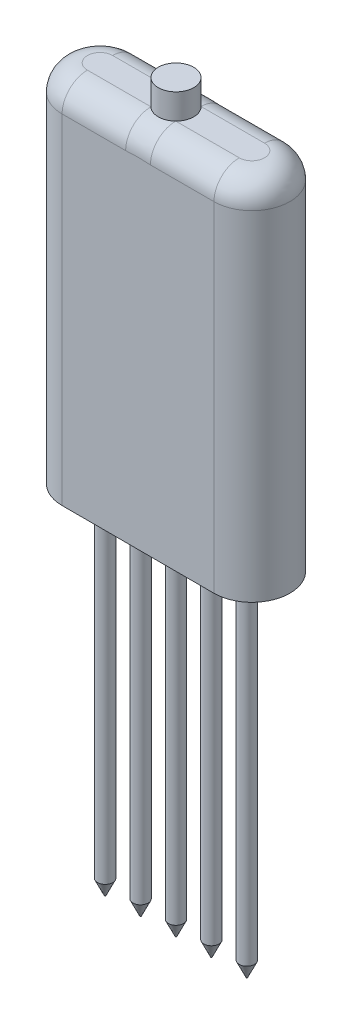
SolidWorks part; units mm, degrees
ref_plane "Front Plane" through (0, 0, 0) normal (0, 0, 1) x (1, 0, 0)
ref_plane "Top Plane" through (0, 0, 0) normal (0, 1, 0) x (1, 0, 0)
ref_plane "Right Plane" through (0, 0, 0) normal (1, 0, 0) x (0, 0, -1)
sketch "Sketch2" plane through (0, 0, 0) normal (0, 1, 0) x (1, 0, 0)
  line L1 (-15, 7.5) -> (15, 7.5)
  line L3 (-15, -7.5) -> (15, -7.5)
  arc A0 (-15, 7.5) -> (-15, -7.5) centre (-15, 0) ccw
  arc A1 (15, 7.5) -> (15, -7.5) centre (15, 0) cw
  point P4 (0, 7.5)
  point P7 (0, 0)
  dimension "D2" = 30
  dimension "D1" = 15
extrude "Boss-Extrude1" add sketch "Sketch2" along normal blind 72
sketch "Sketch3" plane through (0, 0, 0) normal (0, -1, 0) x (1, 0, 0)
  line L0 (24.75, 0) -> (-24.75, 0) construction
  circle A0 centre (-14, 0) radius 1.5
  circle A1 centre (-7, 0) radius 1.5
  circle A2 centre (0, 0) radius 1.5
  circle A3 centre (7, 0) radius 1.5
  circle A4 centre (14, 0) radius 1.5
  dimension "D1" = 3
  dimension "D3" = 7
  dimension "D2" = 5
extrude "Boss-Extrude2" add sketch "Sketch3" along normal blind 67
sketch "Sketch4" plane through (0, -67, 0) normal (0, -1, 0) x (1, 0, 0)
  circle A0 centre (14, 0) radius 1.5 construction
  circle A1 centre (7, 0) radius 1.5 construction
  circle A2 centre (0, 0) radius 1.5 construction
  circle A3 centre (-7, 0) radius 1.5 construction
  circle A4 centre (-14, 0) radius 1.5 construction
  circle A5 centre (14, 0) radius 1.5
  circle A6 centre (7, 0) radius 1.5
  circle A7 centre (0, 0) radius 1.5
  circle A8 centre (-7, 0) radius 1.5
  circle A9 centre (-14, 0) radius 1.5
extrude "Boss-Extrude3" add sketch "Sketch4" along normal blind 3 draft 25
sketch "Sketch5" plane through (0, 72, 0) normal (0, 1, 0) x (1, 0, 0)
  circle A0 centre (0, 0) radius 3.5
  dimension "D1" = 7
extrude "Boss-Extrude4" add sketch "Sketch5" along normal blind 5
fillet "Fillet1" radius 5 4 edges at (0, 72, -7.5) (0, 72, 7.5) (-22.5, 72, 0) (22.5, 72, 0)
